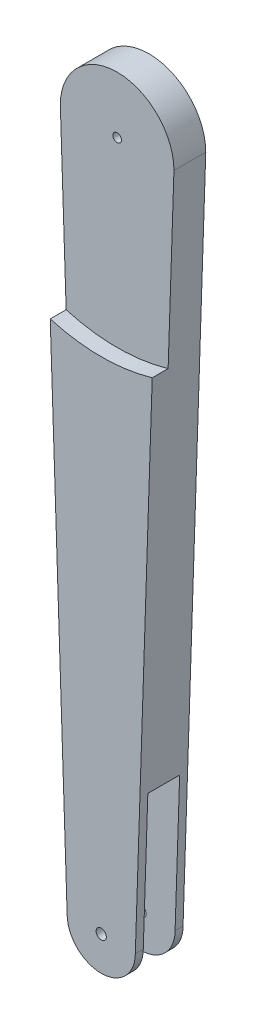
SolidWorks part; units mm, degrees
ref_plane "Front Plane" through (0, 0, 0) normal (0, 0, 1) x (1, 0, 0)
ref_plane "Top Plane" through (0, 0, 0) normal (0, 1, 0) x (1, 0, 0)
ref_plane "Right Plane" through (0, 0, 0) normal (1, 0, 0) x (0, 0, -1)
sketch "Sketch2" plane through (0, 0, 0) normal (0, 0, 1) x (1, 0, 0)
  line L1 (15, -300) -> (25, 0)
  line L2 (-15, -300) -> (-25, 0)
  line L3 (0, -300) -> (0, -397.2479)
  line L4 (0, -270) -> (0, -300)
  arc A2 (25, 0) -> (-25, 0) centre (0, 0) ccw
  arc A4 (-15, -300) -> (15, -300) centre (0, -300) ccw
  dimension "D1" = 300
  dimension "D2" = 50
  dimension "D3" = 15
extrude "Boss-Extrude1" add sketch "Sketch2" along normal blind 21 contours L2 A4 L1 A2 region at (0, -131.0715, 0)
sketch "Sketch3" plane through (0, 0, 21) normal (0, 0, 1) x (1, 0, 0)
  circle A0 centre (0, 0) radius 80
  dimension "D1" = 160
extrude "Cut-Extrude1" cut sketch "Sketch3" against normal blind 7
ref_plane "Plane1" through (0, 0, 10.5) normal (0, 0, 1) x (1, 0, 0)
sketch "Sketch4" plane through (0, 0, 14) normal (0, 0, 1) x (1, 0, 0)
  circle A0 centre (0, 0) radius 1.9
  dimension "D1" = 3.8
extrude "Cut-Extrude2" cut sketch "Sketch4" against normal blind 22.5
sketch "Sketch5" plane through (24.9723, -0.8324, 0) normal (0.9994, -0.0333, 0) x (0, 0, -1)
  line L0 (-21, -314.8335) -> (0, -314.8335) construction
  line L1 (-17.5, -314.8335) -> (-3.5, -314.8335)
  line L2 (-17.5, -314.8335) -> (-17.5, -238.9555)
  line L3 (-17.5, -238.9555) -> (-3.5, -238.9555)
  line L4 (-3.5, -314.8335) -> (-3.5, -238.9555)
  line L5 (-21, -299.3337) -> (-21, -314.8335) construction
  dimension "D1" = 14
  dimension "D2" = 3.5
extrude "Cut-Extrude3" cut sketch "Sketch5" against normal mid plane 218
sketch "Sketch6" plane through (0, 0, 21) normal (0, 0, 1) x (1, 0, 0)
  circle A0 centre (0, -300) radius 2.25
  dimension "D1" = 4.5
extrude "Cut-Extrude4" cut sketch "Sketch6" against normal blind 22
